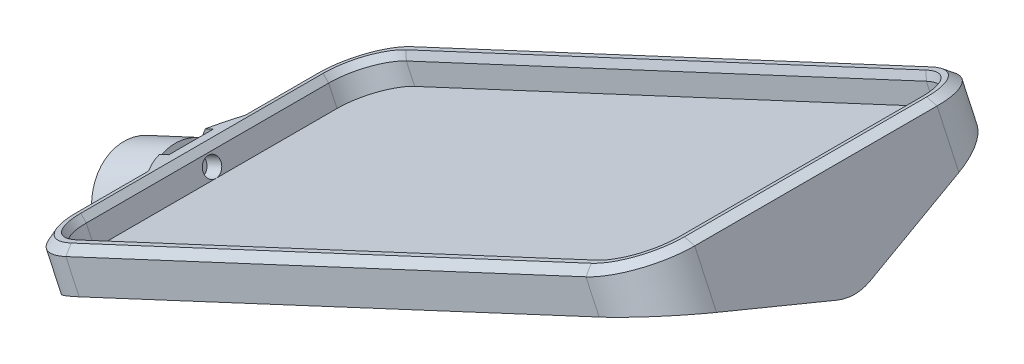
SolidWorks part; units mm, degrees
ref_plane "Alzado" through (0, 0, 0) normal (0, 0, 1) x (1, 0, 0)
ref_plane "Planta" through (0, 0, 0) normal (0, 1, 0) x (1, 0, 0)
ref_plane "Vista lateral" through (0, 0, 0) normal (1, 0, 0) x (0, 0, -1)
sketch "Croquis1" plane through (0, 0, 0) normal (1, 0, 0) x (0, 0, -1)
  circle A0 centre (0, 0) radius 9
  dimension "D1" = 18
extrude "Saliente-Extruir1" add sketch "Croquis1" along normal blind 90
sketch "Croquis2" plane through (90, 0, 0) normal (1, 0, 0) x (0, 0, -1)
  line L0 (-18.2788, 10) -> (25.9849, 10) construction
  circle A1 centre (0, 0) radius 9
  circle A2 centre (0, 0) radius 9
  dimension "D1" = 10
  dimension "D2" = 0
revolve "Revolución1" add sketch "Croquis2" angle 25 about L0 reverse direction yes
sketch "Croquis3" plane through (77.7557, 36.2581, 0) normal (0.9063, 0.4226, 0) x (0, 0, -1)
  circle A1 centre (0, -38.9726) radius 9
  circle A2 centre (0, -38.9726) radius 9
  dimension "D1" = 0
extrude "Saliente-Extruir2" add sketch "Croquis3" along normal blind 140
sketch "Croquis5" plane through (204.6388, 95.4246, 0) normal (0.9063, 0.4226, 0) x (0, 0, -1)
  line L0 (-32.8, -36.8226) -> (-3.0251, -47.4489)
  line L1 (-32.8, -29.8226) -> (32.8, -29.8226)
  line L2 (-32.8, -29.8226) -> (-32.8, -36.8226)
  line L4 (32.8, -29.8226) -> (32.8, -36.8226)
  line L5 (32.8, -36.8226) -> (3.0251, -47.4489)
  circle A1 centre (0, -38.9726) radius 9
  arc A2 (-3.0251, -47.4489) -> (3.0251, -47.4489) centre (0, -38.9726) ccw
  point P7 (0, -29.8226)
  dimension "D2" = 65.6
  dimension "D3" = 7
  dimension "D1" = 0
extrude "Saliente-Extruir3" add sketch "Croquis5" against normal blind 126.6
sketch "Croquis7" plane through (12.6036, -27.0285, 0) normal (-0.4226, 0.9063, 0) x (0.9063, 0.4226, 0)
  line L1 (102.1939, 29.8) -> (222.7939, 29.8)
  line L2 (102.1939, 29.8) -> (102.1939, -29.8)
  line L3 (102.1939, -29.8) -> (222.7939, -29.8)
  line L4 (222.7939, 29.8) -> (222.7939, -29.8)
  line L6 (99.1939, 9) -> (99.1939, -9) construction
  line L7 (99.1939, 32.8) -> (225.7939, 32.8) construction
  point P4 (102.1939, 0)
  point P8 (99.1939, 0)
  point P11 (162.4939, 29.8)
  point P12 (162.4939, 32.8)
  dimension "D1" = 59.6
  dimension "D2" = 120.6
extrude "Cortar-Extruir1" cut sketch "Croquis7" against normal blind 5
fillet "Redondeo2" radius 7.5 4 edges at (215.58, 64.8625, 29.8) (215.58, 64.8625, -29.8) (106.2792, 13.8947, -29.8) (106.2792, 13.8947, 29.8)
fillet "Redondeo1" radius 10.5 4 edges at (218.7215, 65.2241, -32.8) (103.9829, 11.7206, -32.8) (103.9829, 11.7206, 32.8) (218.7215, 65.2241, 32.8)
sketch "Croquis8" plane through (92.6191, 43.189, 0) normal (0.9063, 0.4226, 0) x (0, 0, -1)
  line L0 (22.3, -34.8226) -> (-22.3, -34.8226) construction
  circle A0 centre (0, -33.1726) radius 1.65
  point P5 (0, -34.8226)
  dimension "D1" = 3.3
extrude "Cortar-Extruir2" cut sketch "Croquis8" against normal blind 60
sketch "Croquis9" plane through (12.6036, -27.0285, 0) normal (-0.4226, 0.9063, 0) x (0.9063, 0.4226, 0)
  line L1 (96.1939, 4.3936) -> (99.1939, 4.3936)
  line L2 (96.1939, 4.3936) -> (96.1939, -3.8064)
  line L3 (96.1939, -3.8064) -> (99.1939, -3.8064)
  line L4 (99.1939, 4.3936) -> (99.1939, -3.8064)
  line L5 (99.1939, 22.3) -> (99.1939, -22.3) construction
  dimension "D1" = 8.2
  dimension "D2" = 3
extrude "Cortar-Extruir3" cut sketch "Croquis9" against normal blind 7.6
chamfer "Chaflán1" distance 3 angle 40 2 edges at (106.6883, 5.9189, -8.9686) (106.5492, 6.2173, 8.9901) first distance on face at (94.2262, 0.9369, -9)
sketch "Croquis10" plane through (89.9002, 41.9211, 0) normal (-0.9063, -0.4226, 0) x (0, 0, 1)
  circle A2 centre (0, -33.1726) radius 3.05
  dimension "D1" = 6.1
extrude "Cortar-Extruir4" cut sketch "Croquis10" along normal blind 58.6 from offset 20
chamfer "Chaflán2" distance 1.5 angle 40 9 edges at (102.5038, 14.8927, 14.6474) (105.291, 16.1924, 29.7246) (159.8731, 41.6444, 32.8) (214.4551, 67.0964, 29.7246) (102.5038, 14.8927, -14.6474) (217.2423, 68.3961, 0) (105.291, 16.1924, -29.7246) (214.4551, 67.0964, -29.7246) (159.8731, 41.6444, -32.8) first distance on face at (159.8731, 41.6444, 0)
chamfer "Chaflán3" distance 0.5 angle 70 8 edges at (105.2227, 16.1605, 0) (107.2136, 17.0889, 27.6033) (107.2136, 17.0889, -27.6033) (159.8731, 41.6444, 29.8) (159.8731, 41.6444, -29.8) (212.5325, 66.1999, 27.6033) (212.5325, 66.1999, -27.6033) (214.5234, 67.1283, 0) first distance on face at (135.2686, 30.1711, -0.0629)
sketch "Croquis11" plane through (0, 0, 0) normal (0, 0, 1) x (1, 0, 0)
  line L0 (80.8975, 29.5203) -> (107.4995, -27.5278)
  line L1 (107.4995, -27.5278) -> (-25.3879, -27.5278)
  line L2 (-25.3879, -27.5278) -> (-25.3879, 29.5203)
  line L3 (-25.3879, 29.5203) -> (80.8975, 29.5203)
  line L4 (90.4226, 9.0937) -> (98.0297, -7.2198) construction
extrude "Cortar-Extruir5" cut sketch "Croquis11" against normal blind 10 and the other way blind 10
